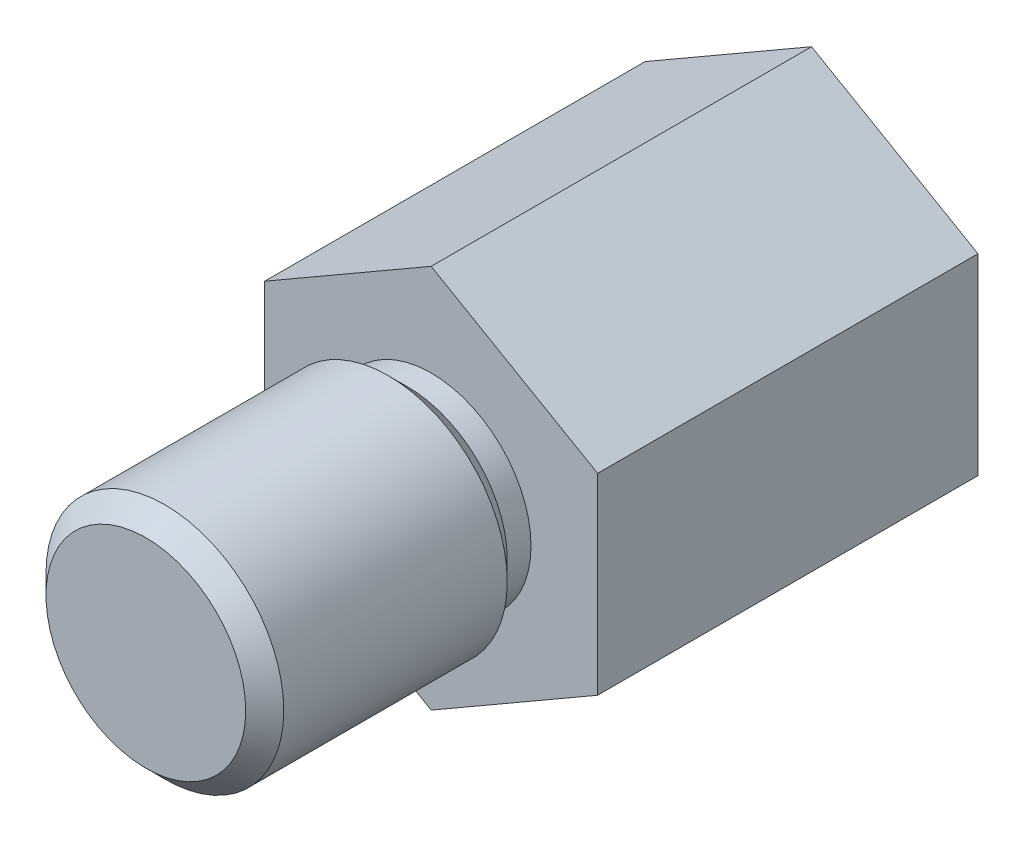
SolidWorks part; units mm, degrees
ref_plane "Спереди" through (0, 0, 0) normal (0, 0, 1) x (1, 0, 0)
ref_plane "Сверху" through (0, 0, 0) normal (0, 1, 0) x (1, 0, 0)
ref_plane "Справа" through (0, 0, 0) normal (1, 0, 0) x (0, 0, -1)
sketch "Эскиз1" plane through (0, 0, 0) normal (0, 0, 1) x (1, 0, 0)
  line L1 (0, 4.0415) -> (-3.5, 2.0207)
  line L2 (-3.5, 2.0207) -> (-3.5, -2.0207)
  line L3 (-3.5, -2.0207) -> (0, -4.0415)
  line L4 (0, -4.0415) -> (3.5, -2.0207)
  line L5 (3.5, -2.0207) -> (3.5, 2.0207)
  line L6 (3.5, 2.0207) -> (0, 4.0415)
  circle A0 centre (0, 0) radius 3.5 construction
  dimension "D1" = 7
extrude "Вытянуть1" add sketch "Эскиз1" along normal blind 8
sketch "Эскиз2" plane through (0, 0, 8) normal (0, 0, 1) x (1, 0, 0)
  circle A0 centre (0, 0) radius 2.5
  dimension "D1" = 5
extrude "Вытянуть2" add sketch "Эскиз2" along normal blind 6
sketch "Эскиз3" plane through (0, 0, 8) normal (0, 0, 1) x (1, 0, 0)
  circle A0 centre (0, 0) radius 2.1
  circle A1 centre (0, 0) radius 2.5 construction
  circle A2 centre (0, 0) radius 2.5
  dimension "D1" = 4.2
extrude "Вырез-Вытянуть3" cut sketch "Эскиз3" along normal blind 0.5
chamfer "Фаска1" distance 0.4 angle 45
hole_wizard "Отверстие с зазором M41" positions "Трехмерный эскиз2" profile "Эскиз5" hole size "M4" standard "Ansi Метрический"
sketch3d "Трехмерный эскиз2"
  point P0 (0, 0, 0)
  point P2 (0, 0, 0)
  point P3 (0, 0, 0)
sketch "Эскиз5" plane through (0, 0, 0) normal (1, 0, 0) x (0, 1, 0)
  line L0 (0, 0) -> (0, 6.9914)
  line L1 (0, 6.9914) -> (1.65, 6)
  line L2 (1.65, 6) -> (1.65, 0.35)
  line L3 (1.65, 0.35) -> (2, 0)
  line L5 (2, 0) -> (0, 0)
  line L6 (-1.65, 0.35) -> (-2, 0) construction
  line L10 (0, 6.9914) -> (-1.65, 6) construction
  line L11 (0, -6.35) -> (0, 107.95) construction
  dimension "Диаметр отверстия" = 3.3
  dimension "Глубина отверстия" = 6
  dimension "Диаметр передней зенковки" = 4
  dimension "Угол передней зенковки" = 90
  dimension "Угол заточки сверла" = 118
cosmetic thread "Условное изображение резьбы1" parameters "D1"=5, "D2"=4
